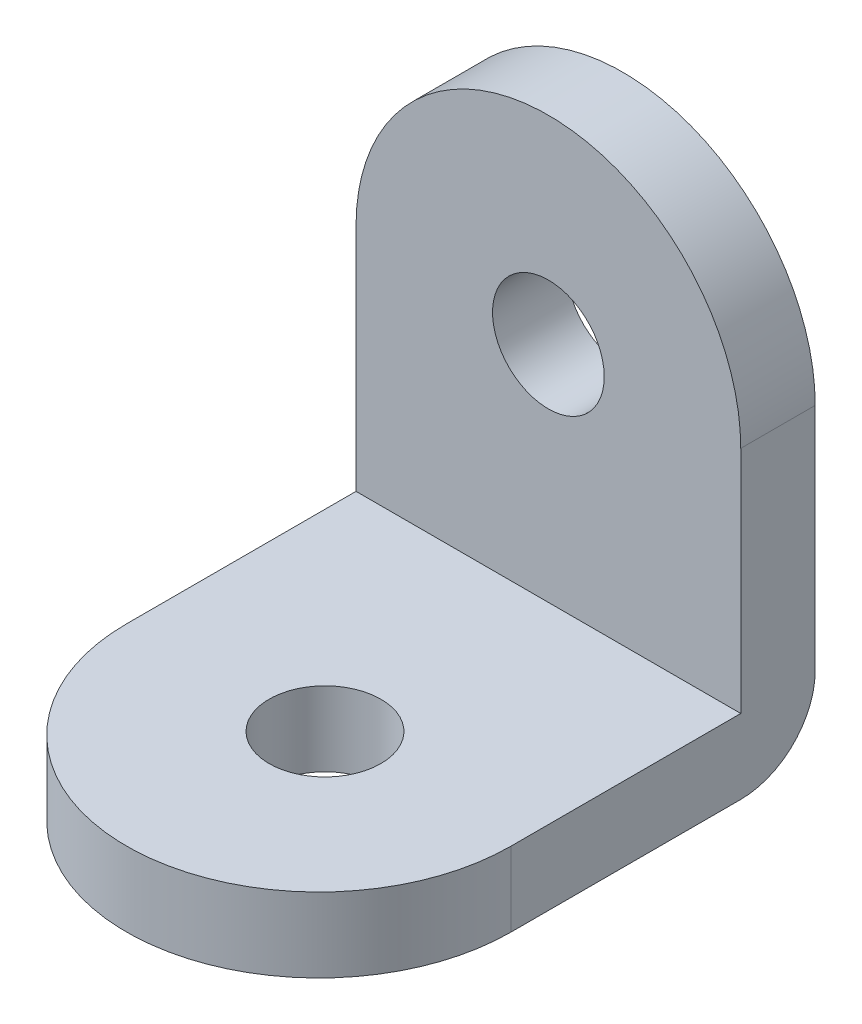
SolidWorks part; units mm, degrees
ref_plane "Front Plane" through (0, 0, 0) normal (0, 0, 1) x (1, 0, 0)
ref_plane "Top Plane" through (0, 0, 0) normal (0, 1, 0) x (1, 0, 0)
ref_plane "Right Plane" through (0, 0, 0) normal (1, 0, 0) x (0, 0, -1)
sketch "Sketch1" plane through (0, 0, 0) normal (0, 0, 1) x (1, 0, 0)
  line L1 (-7.75, 6.125) -> (7.75, 6.125) construction
  line L2 (-7.75, 6.125) -> (-7.75, -6.125)
  line L3 (-7.75, -6.125) -> (7.75, -6.125)
  line L4 (7.75, 6.125) -> (7.75, -6.125)
  line L5 (-7.75, 6.125) -> (7.75, -6.125) construction
  line L6 (-7.75, -6.125) -> (7.75, 6.125) construction
  arc A0 (-7.75, 6.125) -> (7.75, 6.125) centre (0, 6.125) cw
  circle A1 centre (0, 5.875) radius 2.25
  point P0 (0, 0)
  dimension "D4" = 4.5
  dimension "D1" = 15.5
  dimension "D2" = 12.25
  dimension "D3" = 0.25
extrude "Boss-Extrude1" add sketch "Sketch1" along normal blind 3
ref_plane "Plane1" through (0, 0, 1.5) normal (0, 0, 1) x (1, 0, 0)
ref_plane "Plane2" through (0, -4.625, 0) normal (0, -1, 0) x (-1, 0, 0)
ref_axis "Axis1" through (-8.525, -4.625, 1.5) along (1, 0, 0)
pattern_circular "CirPattern1" count 2 every 90 about axis through (-8.525, -4.625, 1.5) along (1, 0, 0) of "Boss-Extrude1"
fillet "Fillet1" radius 3 1 edges at (0, -6.125, 0)
